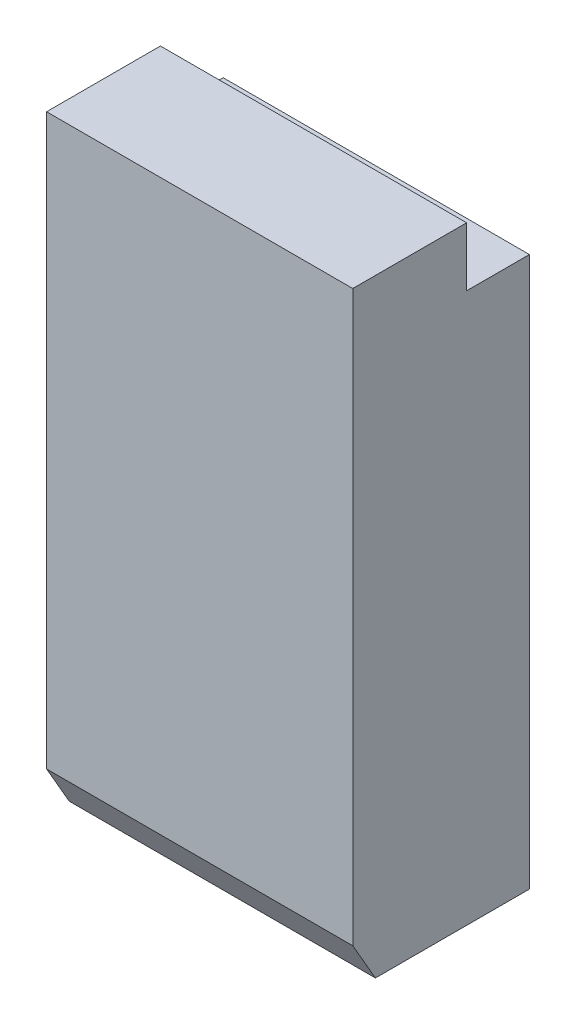
SolidWorks part; units mm, degrees
ref_plane "Спереди" through (0, 0, 0) normal (0, 0, 1) x (1, 0, 0)
ref_plane "Сверху" through (0, 0, 0) normal (0, 1, 0) x (1, 0, 0)
ref_plane "Справа" through (0, 0, 0) normal (1, 0, 0) x (0, 0, -1)
sketch "Эскиз1" plane through (0, 0, 0) normal (1, 0, 0) x (0, 0, -1)
  line L0 (0, 0) -> (0, 1.5)
  line L1 (0, 1.5) -> (2.9, 1.5)
  line L2 (2.9, 1.5) -> (2.9, 0)
  line L3 (2.9, 0) -> (4.5, 0)
  line L4 (4.5, 0) -> (4.5, -14)
  line L5 (4.5, -14) -> (0, -14)
  line L6 (0, -14) -> (0, 0)
  line L7 (2.9, 0) -> (0, 0) construction
  dimension "D1" = 2.9
  dimension "D2" = 1.5
  dimension "D3" = 4.5
  dimension "D4" = 14
extrude "Бобышка-Вытянуть1" add sketch "Эскиз1" along normal mid plane 7.8
chamfer "Фаска1" distance 1 angle 30 1 edges at (0, -14, 0) first distance on face at (0, -6.25, 0)
